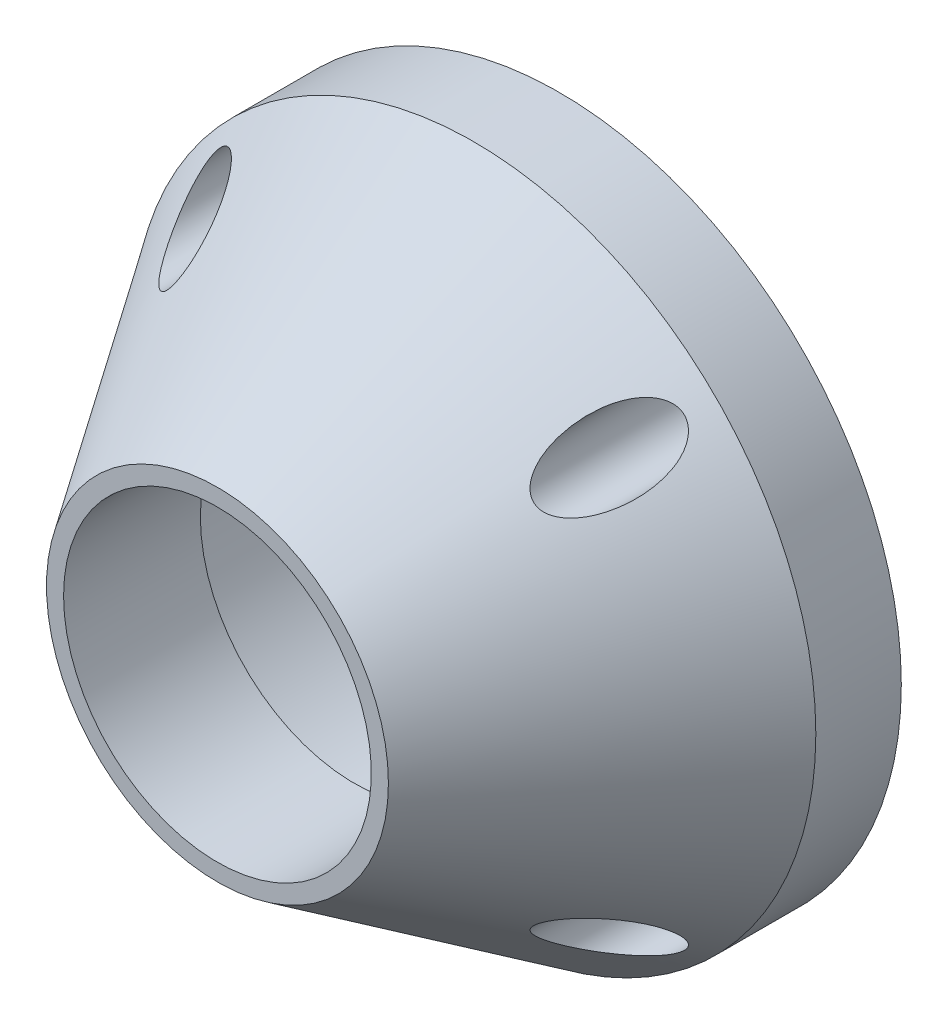
SolidWorks part; units mm, degrees
ref_plane "Front Plane" through (0, 0, 0) normal (1, 0, 0) x (0, 1, 0)
ref_plane "Top Plane" through (0, 0, 0) normal (0, 0, 1) x (0, 1, 0)
ref_plane "Right Plane" through (0, 0, 0) normal (0, 1, 0) x (-1, 0, 0)
sketch "Sketch6" plane through (0, 0, 0) normal (1, 0, 0) x (0, 1, 0)
  line L0 (0, 0) -> (-100, 0)
  line L1 (-100, 0) -> (-100, 25)
  line L2 (-100, 25) -> (-50, 100)
  line L3 (-50, 100) -> (0, 100)
  line L4 (0, 100) -> (0, 0)
  dimension "D1" = 25
  dimension "D2" = 100
  dimension "D3" = 50
  dimension "D4" = 100
revolve "Revolve1" add sketch "Sketch6" angle 360 about L4
sketch "Sketch7" plane through (0, 0, 0) normal (0, 1, 0) x (-1, 0, 0)
  line L0 (0, 25) -> (-45, 25)
  line L1 (-100, 25) -> (100, 25) construction
  line L3 (50, 100) -> (-50, 100) construction
  line L4 (0, 25) -> (0, 100)
  line L5 (-45, 100) -> (0, 100)
  line L6 (-45, 25) -> (-60, 25)
  line L7 (-60, 25) -> (-60, 60)
  line L8 (-60, 60) -> (-45, 60)
  line L9 (-45, 100) -> (-45, 60)
  dimension "D1" = 45
  dimension "D2" = 15
  dimension "D3" = 35
  dimension "D4" = 45
revolve "Cut-Revolve1" cut sketch "Sketch7" angle 360 about L4
sketch "Sketch8" plane through (0, 0, 100) normal (0, 0, 1) x (1, 0, 0)
  line L0 (-60.7107, -60.7107) -> (-60.7107, 60.7107)
  line L1 (70.7107, -70.7107) -> (-70.7107, -70.7107)
  line L2 (70.7107, -70.7107) -> (70.7107, 70.7107)
  line L3 (70.7107, 70.7107) -> (-70.7107, 70.7107)
  line L4 (-70.7107, -70.7107) -> (-70.7107, 70.7107)
  line L5 (70.7107, -70.7107) -> (-70.7107, 70.7107) construction
  line L6 (70.7107, 70.7107) -> (-70.7107, -70.7107) construction
  line L7 (60.7107, 60.7107) -> (-60.7107, 60.7107)
  line L8 (60.7107, -60.7107) -> (60.7107, 60.7107)
  line L9 (60.7107, -60.7107) -> (-60.7107, -60.7107)
  circle A0 centre (0, 0) radius 100 construction
  circle A1 centre (-60.7107, 60.7107) radius 4
  circle A2 centre (60.7107, 60.7107) radius 4
  circle A3 centre (60.7107, -60.7107) radius 4
  circle A4 centre (-60.7107, -60.7107) radius 4
  circle A5 centre (-60.7107, 60.7107) radius 10
  circle A6 centre (60.7107, 60.7107) radius 10
  circle A7 centre (60.7107, -60.7107) radius 10
  circle A8 centre (-60.7107, -60.7107) radius 10
  point P0 (0, 0)
  point P22 (0, 0)
  point P29 (0, 0)
  dimension "D2" = 8
  dimension "D4" = 4
  dimension "D1" = 10
  dimension "D3" = 4
extrude "Cut-Extrude1" cut sketch "Sketch8" against normal blind 121 contours A4 | A3 | A2 | A1
extrude "Cut-Extrude2" cut sketch "Sketch8<9>" against normal blind 90 contours A5 | A6 | A7 | A8
sketch "Sketch8<9>" plane through (0, 0, 100) normal (0, 0, 1) x (1, 0, 0) same geometry as "Sketch8"
